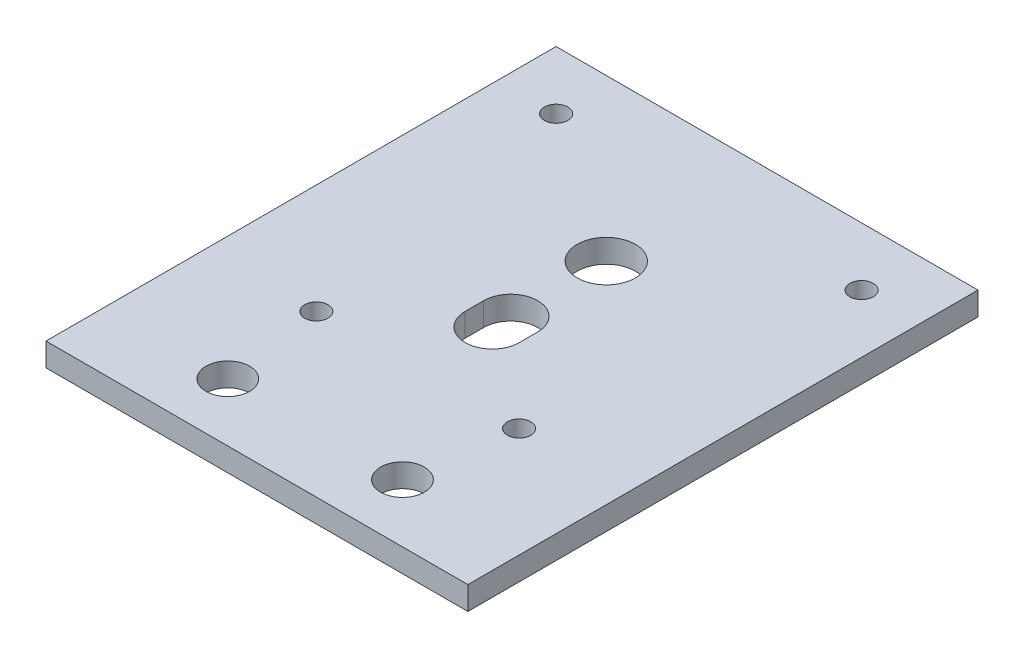
SolidWorks part; units mm, degrees
ref_plane "Front Plane" through (0, 0, 0) normal (0, 0, 1) x (1, 0, 0)
ref_plane "Top Plane" through (0, 0, 0) normal (0, 1, 0) x (1, 0, 0)
ref_plane "Right Plane" through (0, 0, 0) normal (1, 0, 0) x (0, 0, -1)
sketch "Sketch1" plane through (0, 0, 0) normal (0, 1, 0) x (1, 0, 0)
  line L0 (186.7062, -778.1024) -> (-171.2698, -778.1024)
  arc A0 (-12.9178, -1344.2422) -> (28.3543, -1344.2422) centre (7.7182, -1335.303) ccw
  spline S0 degree 3 poles (28.3543, -1344.2422) (38.1207, -1321.6964) (44.9392, -1298.0794) (60.8237, -1251.6716) (68.5445, -1228.3934) (91.0292, -1158.3687) (105.1224, -1111.4203) (144.7238, -969.7826) (167.5373, -874.3159) (186.7062, -778.1024) knots 0 0 0 0 0.125 0.125 0.25 0.25 0.5 0.5 1 1 1 1
  spline S1 degree 3 poles (-171.2698, -778.1024) (-159.7078, -836.1348) (-146.8189, -893.9188) (-132.6111, -951.3608) (-118.4033, -1008.8028) (-102.8733, -1065.9339) (-86.0456, -1122.6638) (-74.9901, -1159.9341) (-63.3713, -1197.0419) (-51.1942, -1233.961) (-45.1006, -1252.436) (-38.8668, -1270.8654) (-32.4946, -1289.2462) (-26.1208, -1307.6316) (-20.6525, -1326.3867) (-12.9178, -1344.2422) knots 0 0 0 0 0.177519 0.177519 0.177519 0.355038 0.355038 0.355038 0.471647 0.471647 0.471647 0.529995 0.529995 0.529995 0.588358 0.588358 0.588358 0.588358
extrude "Boss-Extrude1" add sketch "Sketch1" along normal blind 5.08 contours S1 A0 S0 L0
hole_wizard "3/8 (0.375) Diameter Hole1" positions "Sketch2" profile "Sketch3" hole size "3/8" standard "ANSI Inch" end condition through all
sketch "Sketch2" plane through (0, 5.08, 0) normal (0, 1, 0) x (1, 0, 0)
  line L0 (7.7182, -1357.792) -> (7.7182, -1326.042)
  line L1 (7.7182, -1326.042) -> (7.7182, -1300.642)
  arc A0 (-12.9178, -1344.2422) -> (28.3543, -1344.2422) centre (7.7182, -1335.303) ccw construction
  arc A1 (-12.9178, -1344.2422) -> (28.3543, -1344.2422) centre (7.7182, -1335.303) ccw
  point P0 (7.7182, -1326.042)
  point P2 (7.7182, -1300.642)
  dimension "D1" = 31.75
  dimension "D2" = 25.4
sketch "Sketch3" plane through (7.7182, 5.08, 1326.042) normal (1, 0, 0) x (0, 0, 1)
  line L0 (0, 0) -> (0, 5.08)
  line L1 (0, 5.08) -> (4.7625, 5.08)
  line L2 (4.7625, 5.08) -> (4.7625, 0)
  line L5 (4.7625, 0) -> (0, 0)
  line L11 (0, -6.35) -> (0, 107.95) construction
  dimension "Thru Hole Dia." = 9.525
  dimension "Thru Hole Depth" = 5.08
hole_wizard "3/8 (0.375) Diameter Hole2" positions "Sketch5" profile "Sketch6" hole size "3/8" standard "ANSI Inch" end condition through all
sketch "Sketch5" plane through (0, 5.08, 0) normal (0, 1, 0) x (1, 0, 0)
  line L0 (7.7182, -778.1024) -> (7.7182, -1357.792) construction
  line L1 (186.7062, -778.1024) -> (-171.2698, -778.1024) construction
  line L3 (-11.3318, -1205.392) -> (26.7682, -1205.392)
  line L10 (64.8682, -1008.542) -> (-49.4318, -1008.542)
  line L11 (64.8682, -1008.542) -> (64.8682, -970.442)
  line L12 (64.8682, -970.442) -> (-49.4318, -970.442)
  line L13 (-49.4318, -1008.542) -> (-49.4318, -970.442)
  line L14 (64.8682, -1008.542) -> (-49.4318, -970.442) construction
  line L15 (64.8682, -970.442) -> (-49.4318, -1008.542) construction
  arc A0 (-12.9178, -1344.2422) -> (28.3543, -1344.2422) centre (7.7182, -1335.303) ccw construction
  point P0 (-49.4318, -970.442)
  point P2 (-49.4318, -1008.542)
  point P4 (64.8682, -970.442)
  point P6 (64.8682, -1008.542)
  point P8 (-11.3318, -1205.392)
  point P10 (26.7682, -1205.392)
  point P27 (7.7182, -1205.392)
  point P89 (7.7182, -989.492)
  point P90 (64.8682, -989.492)
  dimension "D1" = 38.1
  dimension "D2" = 152.4
  dimension "D3" = 38.1
  dimension "D4" = 114.3
  dimension "D5" = 215.9
sketch "Sketch6" plane through (-49.4318, 5.08, 970.442) normal (1, 0, 0) x (0, 0, 1)
  line L0 (0, 0) -> (0, 5.08)
  line L1 (0, 5.08) -> (4.7625, 5.08)
  line L2 (4.7625, 5.08) -> (4.7625, 0)
  line L5 (4.7625, 0) -> (0, 0)
  line L11 (0, -6.35) -> (0, 107.95) construction
  dimension "Thru Hole Dia." = 9.525
  dimension "Thru Hole Depth" = 5.08
sketch "Sketch8" plane through (0, 5.08, 0) normal (0, 1, 0) x (1, 0, 0)
  line L0 (7.7182, -1357.792) -> (7.7182, -778.1024) construction
  line L1 (186.7062, -778.1024) -> (-171.2698, -778.1024) construction
  line L2 (7.7182, -1166.7648) -> (7.7182, -1162.7393) construction
  line L3 (1.8127, -1166.7648) -> (1.8127, -1162.7393)
  line L4 (13.6237, -1166.7648) -> (13.6237, -1162.7393)
  circle A0 centre (7.7182, -1141.892) radius 6.35
  arc A2 (-12.9178, -1344.2422) -> (28.3543, -1344.2422) centre (7.7182, -1335.303) ccw construction
  arc A3 (1.8127, -1166.7648) -> (13.6237, -1166.7648) centre (7.7182, -1166.7648) ccw
  arc A4 (13.6237, -1162.7393) -> (1.8127, -1162.7393) centre (7.7182, -1162.7393) ccw
  point P11 (7.7182, -1164.752)
  point P16 (13.6237, -1164.752)
  dimension "D2" = 12.7
  dimension "D1" = 11.811
  dimension "D3" = 22.86
  dimension "D4" = 4.0254
  dimension "D5" = 215.9
extrude "Cut-Extrude1" cut sketch "Sketch8" against normal through all
sketch "Sketch9" plane through (0, 5.08, 0) normal (0, 1, 0) x (1, 0, 0)
  line L0 (7.7182, -1166.7648) -> (7.7182, -1162.7393) construction
  line L1 (-14.3969, -1202.0722) -> (29.8334, -1202.0722)
  line L2 (-33.1575, -1186.3302) -> (-44.3543, -1122.8302)
  line L3 (-25.5937, -1100.4722) -> (41.0301, -1100.4722)
  line L4 (48.594, -1186.3302) -> (59.7907, -1122.8302)
  line L5 (-30.3818, -1202.0722) -> (63.733, -1100.4722) construction
  line L6 (-48.2966, -1100.4722) -> (45.8182, -1202.0722) construction
  arc A0 (-25.5937, -1100.4722) -> (-44.3543, -1122.8302) centre (-25.5937, -1119.5222) ccw
  arc A1 (41.0301, -1100.4722) -> (59.7907, -1122.8302) centre (41.0301, -1119.5222) cw
  arc A2 (48.594, -1186.3302) -> (29.8334, -1202.0722) centre (29.8334, -1183.0222) cw
  arc A3 (-33.1575, -1186.3302) -> (-14.3969, -1202.0722) centre (-14.3969, -1183.0222) ccw
  circle A4 centre (-14.3969, -1183.0222) radius 2.5527
  circle A5 centre (29.8334, -1183.0222) radius 2.5527
  circle A6 centre (41.0301, -1119.5222) radius 2.5527
  circle A7 centre (-25.5937, -1119.5222) radius 2.5527
  circle A8 centre (7.7182, -1141.892) radius 6.35 construction
  point P0 (7.7182, -1160.942)
  dimension "D4" = 19.05
  dimension "D5" = 5.1054
  dimension "D1" = 20
  dimension "D2" = 76.2
  dimension "D3" = 101.6
  dimension "D6" = 19.05
extrude "Cut-Extrude2" cut sketch "Sketch9" against normal through all contours A4 | A7 | A6 | A5
sketch "Sketch10" plane through (0, 5.08, 0) normal (0, 1, 0) x (1, 0, 0)
  line L1 (-38.2937, -1218.092) -> (53.7301, -1218.092)
  line L2 (-38.2937, -1218.092) -> (-38.2937, -1106.8222)
  line L3 (-38.2937, -1106.8222) -> (53.7301, -1106.8222)
  line L4 (53.7301, -1218.092) -> (53.7301, -1106.8222)
  line L5 (-38.2937, -1218.092) -> (53.7301, -1106.8222) construction
  line L6 (-38.2937, -1106.8222) -> (53.7301, -1218.092) construction
  circle A0 centre (-11.3318, -1205.392) radius 4.7625 construction
  circle A1 centre (-25.5937, -1119.5222) radius 2.5527 construction
  circle A2 centre (41.0301, -1119.5222) radius 2.5527 construction
  point P0 (7.7182, -1162.4571)
  dimension "D2" = 12.7
  dimension "D4" = 12.7
  dimension "D1" = 12.7
  dimension "D3" = 12.7
extrude "Cut-Extrude3" cut sketch "Sketch10" against normal through all flip side to cut contours L2 L3 L4 L1
equation "\"D4@Sketch8\"=.375*sin(25deg)"
